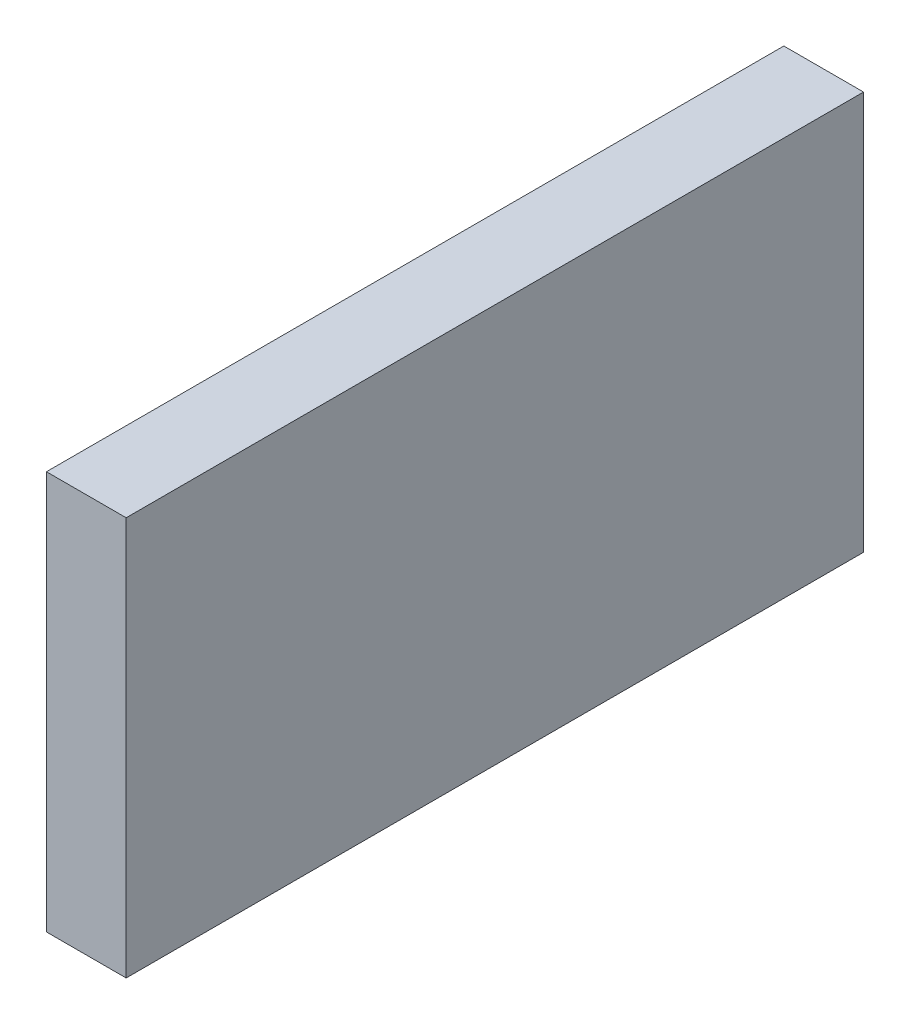
SolidWorks part; units mm, degrees
ref_plane "Front Plane" through (0, 0, 0) normal (0, 0, 1) x (1, 0, 0)
ref_plane "Top Plane" through (0, 0, 0) normal (0, 1, 0) x (1, 0, 0)
ref_plane "Right Plane" through (0, 0, 0) normal (1, 0, 0) x (0, 0, -1)
sketch "Sketch2" plane through (0, 0, 0) normal (1, 0, 0) x (0, 0, -1)
  line L0 (0, 0) -> (0, 20)
  line L1 (0, 20) -> (37, 20)
  line L2 (37, 20) -> (37, 0)
  line L3 (37, 0) -> (0, 0)
  dimension "D1" = 37
  dimension "D2" = 20
extrude "Boss-Extrude1" add sketch "Sketch2" along normal blind 4 contours L3 L0 L1 L2
